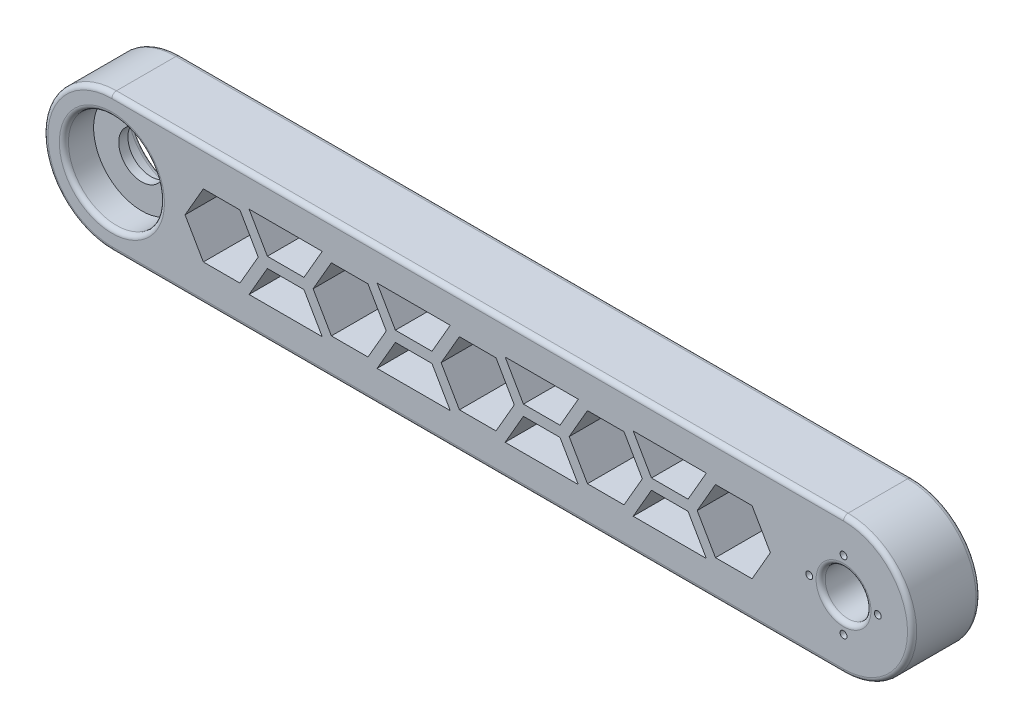
SolidWorks part; units mm, degrees
ref_plane "Front Plane" through (0, 0, 0) normal (0, 0, 1) x (1, 0, 0)
ref_plane "Top Plane" through (0, 0, 0) normal (0, 1, 0) x (1, 0, 0)
ref_plane "Right Plane" through (0, 0, 0) normal (1, 0, 0) x (0, 0, -1)
ref_axis "X" through (-88.99, 0, 0) along (1, 0, 0)
ref_axis "Y" through (0, 55, 0) along (0, -1, 0)
ref_axis "Z" through (0, 0, -88.99) along (0, 0, 1)
sketch "Sketch1" plane through (0, 0, 0) normal (0, 0, 1) x (1, 0, 0)
  line L0 (-80, 0) -> (80, 0) construction
  line L2 (-80, 15) -> (80, 15)
  line L3 (-80, -15) -> (80, -15)
  arc A0 (-80, 15) -> (-80, -15) centre (-80, 0) ccw
  arc A1 (80, -15) -> (80, 15) centre (80, 0) ccw
  circle A2 centre (80, 0) radius 10.5
  circle A3 centre (-80, 0) radius 10.5
  circle A4 centre (-80, 0) radius 5
  circle A5 centre (80, 0) radius 5
  point P5 (0, 0)
  dimension "D2" = 15
  dimension "D3" = 21
  dimension "D4" = 10
  dimension "D1" = 160
extrude "Boss-Extrude1" add sketch "Sketch1" along normal mid plane 2 contours L3 A1 L2 A0 A3 A2 | A4 A3 | A2 A5 region at (0, 0, 0) region at (69.797, 0, 0) region at (-90.203, 0, 0)
extrude "Boss-Extrude2" add sketch "Sketch1<3>" along normal mid plane 15 contours L3 A1 L2 A0 A3 A2 region at (0, 0, 0)
sketch "Sketch1<3>" plane through (0, 0, 0) normal (0, 0, 1) x (1, 0, 0) same geometry as "Sketch1"
sketch "Sketch2" plane through (0, 0, 0) normal (1, 0, 0) x (0, 0, -1)
  line L0 (-7.5, 15) -> (7.5, 15) construction
  line L1 (-7.5, 15) -> (7.5, 15)
  arc A0 (-3, 15) -> (3, 15) centre (0, 15) ccw
  point P6 (0, 15)
  dimension "D1" = 3
extrude "Cut-Extrude1" [suppressed] cut sketch "Sketch2" against normal through all both and the other way through all contours L1 A0
fillet "Fillet1" [suppressed] radius 1
mirror "Mirror3" [suppressed] about plane through (0, 0, 0) normal (0, 1, 0)
sketch "Sketch3" plane through (0, 0, 1) normal (0, 0, 1) x (1, 0, 0)
  circle A1 centre (80, 0) radius 10.5
  circle A2 centre (80, 0) radius 10.5
  circle A3 centre (80, 0) radius 5 construction
  circle A4 centre (80, 0) radius 5
  dimension "D1" = 0
extrude "Boss-Extrude3" add sketch "Sketch3" along normal up to surface (6.5 mm away) up to face at (90.5, 0, 7.5)
fillet "Fillet2" radius 1 12 edges at (-95, 0, 7.5) (0, 15, 7.5) (95, 0, 7.5) (0, -15, 7.5) (-69.5, 0, 7.5) (85, 0, 7.5) (95, 0, -7.5) (0, 15, -7.5) (-95, 0, -7.5) (0, -15, -7.5) (-69.5, 0, -7.5) (90.5, 0, -7.5)
mirror "Mirror1" [suppressed] about plane through (0, 0, 0) normal (1, 0, 0) of bodies 104
delete or keep bodies "Body-Delete/Keep 1" [suppressed] type keep bodies bodies 105
sketch "Sketch4" plane through (0, 0, 7.5) normal (0, 0, 1) x (1, 0, 0)
  circle A18 centre (87.5, 0) radius 0.75 construction
  circle A19 centre (80, -7.5) radius 0.75 construction
  circle A20 centre (72.5, 0) radius 0.75 construction
  circle A21 centre (80, 7.5) radius 0.75 construction
  circle A22 centre (87.5, 0) radius 0.75
  circle A23 centre (80, -7.5) radius 0.75
  circle A24 centre (72.5, 0) radius 0.75
  circle A25 centre (80, 7.5) radius 0.75
extrude "Cut-Extrude2" cut sketch "Sketch4" against normal offset from surface (6.5 mm away) 2 up to face at (85, 0, -1)
sketch "Sketch5" plane through (0, 0, 0) normal (0, 0, 1) x (1, 0, 0)
  line L0 (6, 8.0829) -> (10, 1.1547)
  line L1 (4, -6.9282) -> (8, 0)
  line L2 (8, 0) -> (4, 6.9282)
  line L3 (4, 6.9282) -> (-4, 6.9282)
  line L4 (-4, 6.9282) -> (-8, 0)
  line L5 (-8, 0) -> (-4, -6.9282)
  line L6 (-4, -6.9282) -> (4, -6.9282)
  line L7 (10, 1.1547) -> (18, 1.1547)
  line L8 (18, 1.1547) -> (22, 8.0829)
  line L9 (22, 8.0829) -> (6, 8.0829)
  line L10 (6, 3.4641) -> (8, 4.6188) construction
  line L11 (0, 0) -> (8, 0) construction
  line L12 (10, -1.1547) -> (18, -1.1547)
  line L13 (18, -1.1547) -> (22, -8.0829)
  line L14 (22, -8.0829) -> (6, -8.0829)
  line L15 (6, -8.0829) -> (10, -1.1547)
  circle A0 centre (0, 0) radius 6.9282 construction
  dimension "D1" = 8
  dimension "D2" = 2
extrude "Cut-Extrude3" cut sketch "Sketch5" against normal through all both and the other way through all contours L5 L6 L1 L2 L3 L4 region at (0, 0, 0)
extrude "Cut-Extrude4" cut sketch "Sketch5<3>" against normal through all both and the other way through all contours L15 L14 L13 L12 | L8 L9 L0 L7 region at (14, 5.0037, 0) region at (14, -5.0037, 0)
sketch "Sketch5<3>" plane through (0, 0, 0) normal (0, 0, 1) x (1, 0, 0) same geometry as "Sketch5"
pattern_linear "LPattern1" count 3 spacing 28 along (1, 0, 0) count 3 spacing 28 along (-1, 0, 0) of "Cut-Extrude3"
pattern_linear "LPattern2" count 2 spacing 28 along (1, 0, 0) count 3 spacing 28 along (-1, 0, 0) of "Cut-Extrude4"
